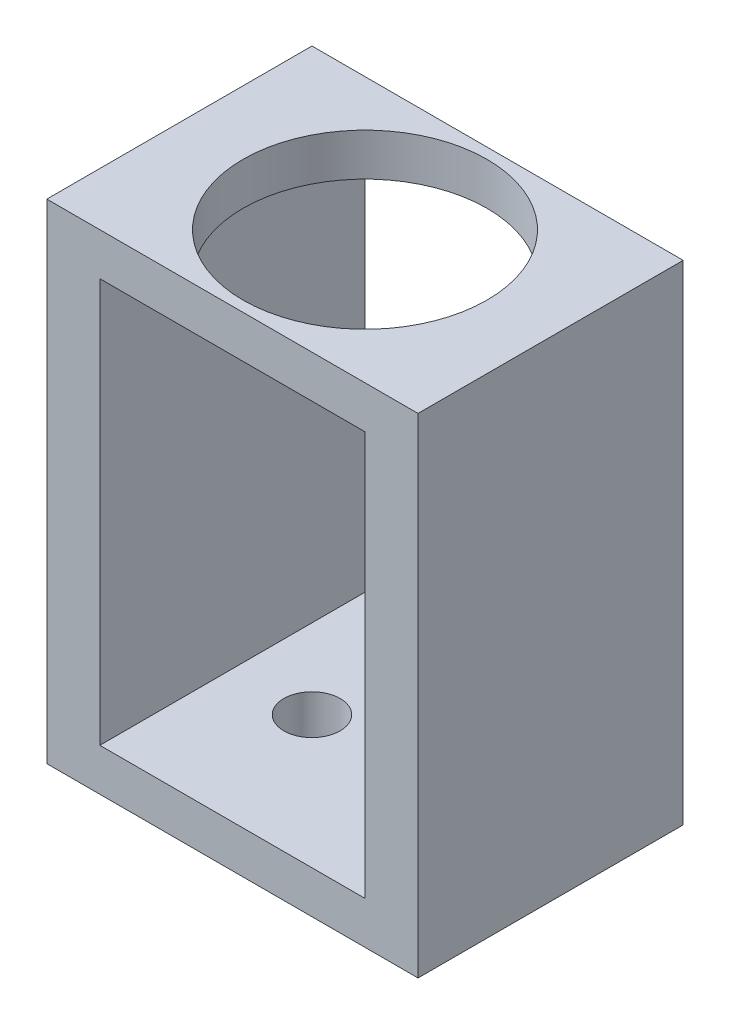
SolidWorks part; units mm, degrees
ref_plane "Front Plane" through (0, 0, 0) normal (0, 0, 1) x (1, 0, 0)
ref_plane "Top Plane" through (0, 0, 0) normal (0, 1, 0) x (1, 0, 0)
ref_plane "Right Plane" through (0, 0, 0) normal (1, 0, 0) x (0, 0, -1)
sketch "Sketch1" plane through (0, 0, 0) normal (0, 1, 0) x (1, 0, 0)
  line L0 (7.5, 12.5) -> (17.5, 12.5) construction
  line L1 (0, 0) -> (25, 0)
  line L2 (0, 0) -> (0, 25)
  line L3 (0, 25) -> (25, 25)
  line L4 (25, 0) -> (25, 25)
  line L5 (0, 12.5) -> (25, 12.5) construction
  line L6 (12.5, 25) -> (12.5, 0) construction
  circle A0 centre (7.5, 12.5) radius 2.65
  circle A1 centre (17.5, 12.5) radius 2.65
  dimension "D2" = 5.3
  dimension "D1" = 10
  dimension "D3" = 25
  dimension "D4" = 25
extrude "Boss-Extrude1" add sketch "Sketch1" along normal blind 4
sketch "Sketch2" plane through (0, 0, 0) normal (0, -1, 0) x (1, 0, 0)
  line L0 (25, -25) -> (0, -25) construction
  line L1 (0, 0) -> (-5, 0)
  line L2 (0, 0) -> (0, -25)
  line L3 (0, -25) -> (-5, -25)
  line L4 (-5, 0) -> (-5, -25)
  line L5 (25, 0) -> (30, 0)
  line L6 (25, 0) -> (25, -25)
  line L7 (25, -25) -> (30, -25)
  line L8 (30, 0) -> (30, -25)
  dimension "D1" = 5
  dimension "D2" = 5
extrude "Boss-Extrude2" add sketch "Sketch2" against normal blind 42.1
sketch "Sketch3" plane through (0, 42.1, 0) normal (0, 1, 0) x (1, 0, 0)
  line L0 (12.5, 25) -> (12.5, 0) construction
  line L1 (-5, 25) -> (30, 25)
  line L2 (-5, 25) -> (-5, 0)
  line L3 (-5, 0) -> (30, 0)
  line L4 (30, 25) -> (30, 0)
  line L5 (-5, 12.5) -> (30, 12.5) construction
  circle A0 centre (12.5, 12.5) radius 11.5
  dimension "D1" = 23
extrude "Boss-Extrude3" add sketch "Sketch3" along normal blind 4
